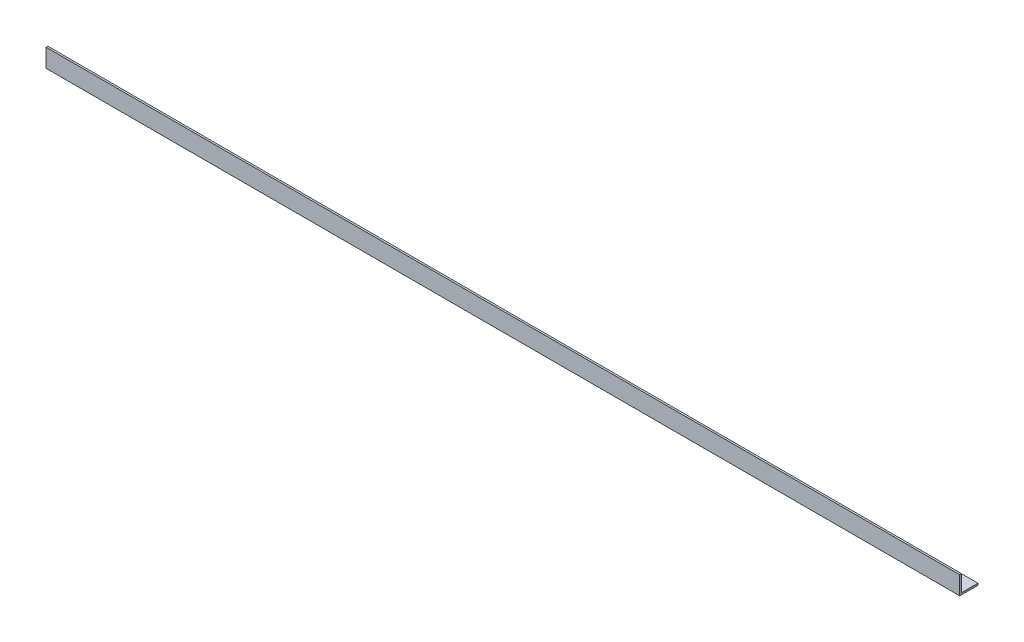
SolidWorks part; units mm, degrees
ref_plane "Спереди" through (0, 0, 0) normal (0, 0, 1) x (1, 0, 0)
ref_plane "Сверху" through (0, 0, 0) normal (0, 1, 0) x (1, 0, 0)
ref_plane "Справа" through (0, 0, 0) normal (1, 0, 0) x (0, 0, -1)
sketch "Эскиз1" plane through (0, 0, 0) normal (1, 0, 0) x (0, 0, -1)
  line L0 (0, 50) -> (0, 0)
  line L1 (0, 0) -> (50, 0)
extrude "Вытянуть-Тонкостенный1" add sketch "Эскиз1" along normal blind 2500 thin thin type one direction reverse wall 5
